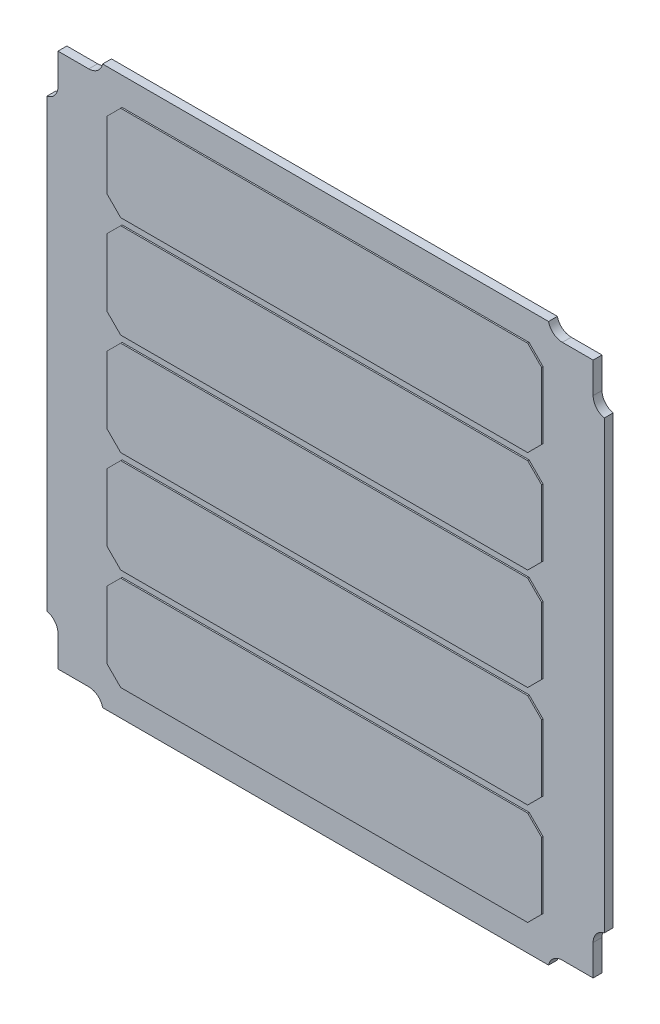
SolidWorks part; units mm, degrees
ref_plane "Front Plane" through (0, 0, 0) normal (0, 0, 1) x (1, 0, 0)
ref_plane "Top Plane" through (0, 0, 0) normal (0, 1, 0) x (1, 0, 0)
ref_plane "Right Plane" through (0, 0, 0) normal (1, 0, 0) x (0, 0, -1)
sketch "Sketch1" plane through (0, 0, 0) normal (0, 0, 1) x (1, 0, 0)
  line L0 (-40, 50) -> (-40, 48)
  line L1 (-50, -50) -> (50, -50)
  line L2 (-50, -50) -> (-50, 50)
  line L3 (-50, 50) -> (50, 50)
  line L4 (50, -50) -> (50, 50)
  line L5 (-50, -50) -> (50, 50) construction
  line L6 (-50, 50) -> (50, -50) construction
  line L7 (-50, 50) -> (-40, 50)
  line L8 (-50, 50) -> (-50, 40)
  line L9 (-40, 48) -> (-48, 48)
  line L10 (-48, 48) -> (-48, 40)
  line L11 (50, 50) -> (40, 50)
  line L12 (50, 50) -> (50, 40)
  line L13 (-48, 40) -> (-50, 40)
  line L14 (50, 40) -> (48, 40)
  line L15 (-50, -50) -> (-37.8649, -50)
  line L16 (-50, -50) -> (-50, -37.8649)
  line L17 (50, 50) -> (50, 40)
  line L18 (50, 50) -> (40, 50)
  line L19 (50, -50) -> (41.5, -50)
  line L20 (50, -50) -> (50, -41.5)
  line L21 (48, 40) -> (48, 48)
  line L22 (48, 48) -> (40, 48)
  line L23 (40, 48) -> (40, 50)
  line L24 (40, -50) -> (40, -48)
  line L25 (50, -50) -> (40, -50)
  line L26 (50, -50) -> (50, -40)
  line L27 (40, -48) -> (48, -48)
  line L28 (48, -48) -> (48, -40)
  line L29 (48, -40) -> (50, -40)
  line L30 (-50, -40) -> (-48, -40)
  line L31 (-50, -50) -> (-50, -40)
  line L32 (-50, -50) -> (-40, -50)
  line L33 (-48, -40) -> (-48, -48)
  line L34 (-48, -48) -> (-40, -48)
  line L35 (-40, -48) -> (-40, -50)
  point P0 (0, 0)
  point P38 (0, 0)
  dimension "D1" = 100
  dimension "D2" = 100
  dimension "D3" = 2
  dimension "D4" = 10
  dimension "D5" = 4
extrude "Boss-Extrude1" add sketch "Sketch1" along normal blind 1.5875 contours L1 L4 L3 L2 region at (0, 0, 0)
sketch "Sketch2" plane through (0, 0, 1.5875) normal (0, 0, 1) x (1, 0, 0)
  line L0 (-36.5, 45) -> (36.5, 45)
  line L1 (-39, 42.5) -> (-36.5, 45)
  line L2 (39, 42.5) -> (39, 30.5)
  line L3 (36.5, 28) -> (-36.5, 28)
  line L4 (-39, 30.5) -> (-39, 42.5)
  line L5 (-36.5, 28) -> (-39, 30.5)
  line L6 (0, 0) -> (0, 50) construction
  line L7 (36.5, 45) -> (39, 42.5)
  line L8 (39, 30.5) -> (36.5, 28)
  line L9 (-36.5, 26.75) -> (36.5, 26.75)
  line L10 (-39, 24.25) -> (-36.5, 26.75)
  line L11 (39, 24.25) -> (39, 12.25)
  line L12 (36.5, 9.75) -> (-36.5, 9.75)
  line L13 (-39, 12.25) -> (-39, 24.25)
  line L14 (-36.5, 9.75) -> (-39, 12.25)
  line L15 (36.5, 26.75) -> (39, 24.25)
  line L16 (39, 12.25) -> (36.5, 9.75)
  line L17 (-36.5, 8.5) -> (36.5, 8.5)
  line L18 (-39, 6) -> (-36.5, 8.5)
  line L19 (39, 6) -> (39, -6)
  line L20 (36.5, -8.5) -> (-36.5, -8.5)
  line L21 (-39, -6) -> (-39, 6)
  line L22 (-36.5, -8.5) -> (-39, -6)
  line L23 (36.5, 8.5) -> (39, 6)
  line L24 (39, -6) -> (36.5, -8.5)
  line L25 (-36.5, -9.75) -> (36.5, -9.75)
  line L26 (-39, -12.25) -> (-36.5, -9.75)
  line L27 (39, -12.25) -> (39, -24.25)
  line L28 (36.5, -26.75) -> (-36.5, -26.75)
  line L29 (-39, -24.25) -> (-39, -12.25)
  line L30 (-40, 50) -> (40, 50) construction
  line L33 (-36.5, -26.75) -> (-39, -24.25)
  line L34 (36.5, -9.75) -> (39, -12.25)
  line L36 (39, -24.25) -> (36.5, -26.75)
  line L37 (-36.5, -28) -> (36.5, -28)
  line L38 (-39, -30.5) -> (-36.5, -28)
  line L39 (39, -30.5) -> (39, -42.5)
  line L40 (36.5, -45) -> (-36.5, -45)
  line L41 (-39, -42.5) -> (-39, -30.5)
  line L42 (-36.5, -45) -> (-39, -42.5)
  line L43 (36.5, -28) -> (39, -30.5)
  line L44 (39, -42.5) -> (36.5, -45)
  line L45 (-40, -50) -> (40, -50) construction
  point P0 (-39, 45)
  point P3 (39, 45)
  point P4 (39, 28)
  point P5 (-39, 28)
  point P19 (-39, 26.75)
  point P21 (39, 26.75)
  point P22 (39, 9.75)
  point P23 (-39, 9.75)
  point P31 (-39, 8.5)
  point P33 (39, 8.5)
  point P34 (39, -8.5)
  point P35 (-39, -8.5)
  point P43 (-39, -9.75)
  point P45 (39, -9.75)
  point P46 (39, -26.75)
  point P47 (-39, -26.75)
  point P55 (-39, -28)
  point P57 (39, -28)
  point P58 (39, -45)
  point P59 (-39, -45)
  dimension "D1" = 78
  dimension "D2" = 17
  dimension "D3" = 5
  dimension "D4" = 5
  dimension "D5" = 5
extrude "Boss-Extrude2" add sketch "Sketch2" along normal blind 0.25
fillet "Fillet1" radius 2.54 8 edges at (-48, -40, 0.7937) (-40, -48, 0.7937) (40, -48, 0.7937) (48, -40, 0.7937) (48, 40, 0.7937) (40, 48, 0.7937) (-40, 48, 0.7937) (-48, 40, 0.7937)
